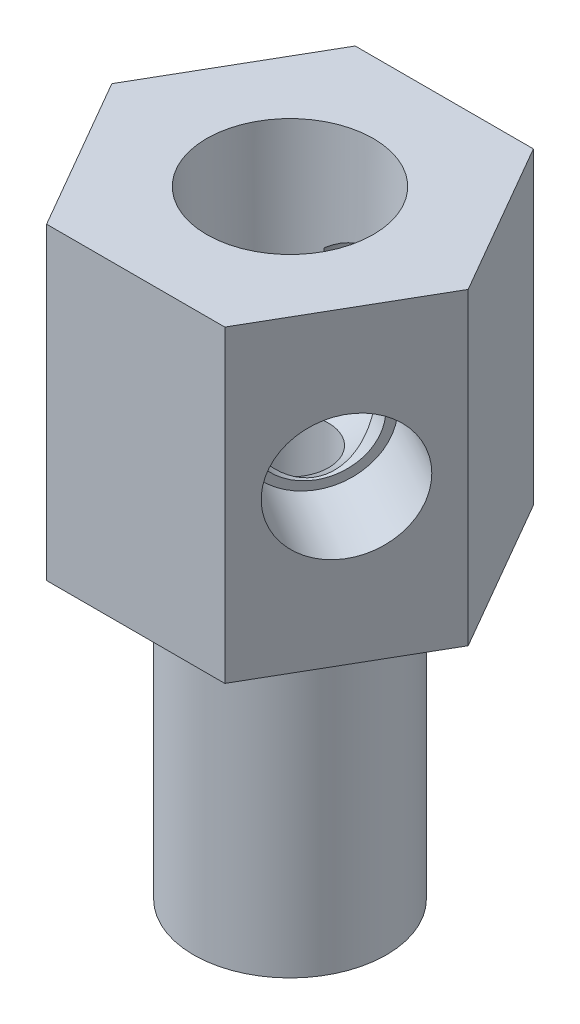
SolidWorks part; units mm, degrees
ref_plane "Front Plane" through (0, 0, 0) normal (0, 0, 1) x (1, 0, 0)
ref_plane "Top Plane" through (0, 0, 0) normal (0, 1, 0) x (1, 0, 0)
ref_plane "Right Plane" through (0, 0, 0) normal (1, 0, 0) x (0, 0, -1)
sketch "Sketch1" plane through (0, 0, 0) normal (0, 1, 0) x (1, 0, 0)
  circle A0 centre (0, 0) radius 7.9375
  dimension "D1" = 15.875
extrude "Boss-Extrude1" add sketch "Sketch1" along normal blind 25.4
cosmetic thread "Cosmetic Thread1" parameters "D2"=14.1961
sketch "Sketch2" plane through (0, 25.4, 0) normal (0, 1, 0) x (1, 0, 0)
  line L1 (14.6647, 0) -> (7.3323, 12.7)
  line L2 (7.3323, 12.7) -> (-7.3323, 12.7)
  line L3 (-7.3323, 12.7) -> (-14.6647, 0)
  line L4 (-14.6647, 0) -> (-7.3323, -12.7)
  line L5 (-7.3323, -12.7) -> (7.3323, -12.7)
  line L6 (7.3323, -12.7) -> (14.6647, 0)
  circle A0 centre (0, 0) radius 12.7 construction
  dimension "D1" = 25.4
extrude "Boss-Extrude2" add sketch "Sketch2" along normal blind 25.4
sketch "Sketch3" plane through (0, 0, 0) normal (0, -1, 0) x (1, 0, 0)
  circle A0 centre (0, 0) radius 3.175
  dimension "D1" = 6.35
extrude "Cut-Extrude1" cut sketch "Sketch3" against normal through all
sketch "Sketch6" plane through (0, 25.4, 0) normal (0, -1, 0) x (1, 0, 0)
  line L0 (-14.6647, 0) -> (-7.3323, 12.7) construction
  line L1 (-7.3323, -12.7) -> (-14.6647, 0) construction
  line L2 (7.3323, -12.7) -> (-7.3323, -12.7) construction
  line L3 (14.6647, 0) -> (7.3323, -12.7) construction
  line L4 (7.3323, 12.7) -> (14.6647, 0) construction
  line L5 (-7.3323, 12.7) -> (7.3323, 12.7) construction
  line L6 (-14.6647, 0) -> (-7.3323, 12.7)
  line L7 (-7.3323, -12.7) -> (-14.6647, 0)
  line L8 (7.3323, -12.7) -> (-7.3323, -12.7)
  line L9 (14.6647, 0) -> (7.3323, -12.7)
  line L10 (7.3323, 12.7) -> (14.6647, 0)
  line L11 (-7.3323, 12.7) -> (7.3323, 12.7)
  circle A0 centre (0, 0) radius 6.6675
  dimension "D1" = 13.335
extrude "Cut-Extrude2" cut sketch "Sketch6" along normal blind 2.3813
hole_wizard "1/4 NPT Tapped Hole1" positions "Sketch5" profile "Sketch4" size "1/4" standard "ANSI Inch"
sketch "Sketch5" plane through (0, 50.8, 0) normal (0, 1, 0) x (1, 0, 0)
  point P0 (0, 0)
sketch "Sketch4" plane through (0, 50.8, 0) normal (1, 0, 0) x (0, 0, 1)
  line L0 (0, 0) -> (0, 20.3603)
  line L1 (5.5626, 17.018) -> (0, 20.3603)
  line L2 (-5.5626, 17.018) -> (0, 20.3603) construction
  line L3 (5.5626, 17.018) -> (5.5626, 9.906)
  line L4 (5.5626, 9.906) -> (6.558, 9.906)
  line L5 (6.558, 9.906) -> (6.8546, 0)
  line L6 (-6.558, 9.906) -> (-6.8546, 0) construction
  line L7 (6.8546, 0) -> (0, 0)
  line L8 (0, -6.35) -> (0, 107.95) construction
  line L11 (-5.5626, 9.906) -> (-6.558, 9.906) construction
  dimension "Tap Drill Dia." = 11.1252
  dimension "Tap Drill Depth" = 17.018
  dimension "Thread Dia." = 13.7092
  dimension "Thread Angle" = 3.43
  dimension "Thread Depth" = 9.906
  dimension "Drill Angle" = 118
hole_wizard "1/8 NPT Tapped Hole1" positions "3DSketch1" profile "Sketch9" size "1/8" standard "ANSI Inch"
sketch3d "3DSketch1"
  line L8 (10.9985, 25.4, 6.35) -> (10.9985, 50.8, 6.35) construction
  line L9 (7.3323, 25.4, 12.7) -> (14.6647, 25.4, 0) construction
  line L10 (7.3323, 50.8, 12.7) -> (14.6647, 50.8, 0) construction
  line L12 (-10.9985, 25.4, 6.35) -> (-10.9985, 50.8, 6.35) construction
  line L13 (-14.6647, 25.4, 0) -> (-7.3323, 25.4, 12.7) construction
  line L14 (-14.6647, 50.8, 0) -> (-7.3323, 50.8, 12.7) construction
  line L16 (0, 50.8, -12.7) -> (0, 25.4, -12.7) construction
  line L17 (7.3323, 50.8, -12.7) -> (-7.3323, 50.8, -12.7) construction
  line L18 (7.3323, 25.4, -12.7) -> (-7.3323, 25.4, -12.7) construction
  point P0 (10.9985, 38.1, 6.35)
  point P2 (0, 38.1, -12.7)
  point P4 (-10.9985, 38.1, 6.35)
sketch "Sketch9" plane through (10.9985, 38.1, 6.35) normal (0, 1, 0) x (0.5, 0, -0.866)
  line L0 (0, 0) -> (0, 14.2175)
  line L1 (4.2164, 11.684) -> (0, 14.2175)
  line L2 (-4.2164, 11.684) -> (0, 14.2175) construction
  line L3 (4.2164, 11.684) -> (4.2164, 6.858)
  line L4 (4.2164, 6.858) -> (4.9362, 6.858)
  line L5 (4.9362, 6.858) -> (5.1415, 0)
  line L6 (-4.9362, 6.858) -> (-5.1415, 0) construction
  line L7 (5.1415, 0) -> (0, 0)
  line L8 (0, -6.35) -> (0, 107.95) construction
  line L11 (-4.2164, 6.858) -> (-4.9362, 6.858) construction
  dimension "Tap Drill Dia." = 8.4328
  dimension "Tap Drill Depth" = 11.684
  dimension "Thread Dia." = 10.283
  dimension "Thread Angle" = 3.43
  dimension "Thread Depth" = 6.858
  dimension "Drill Angle" = 118
